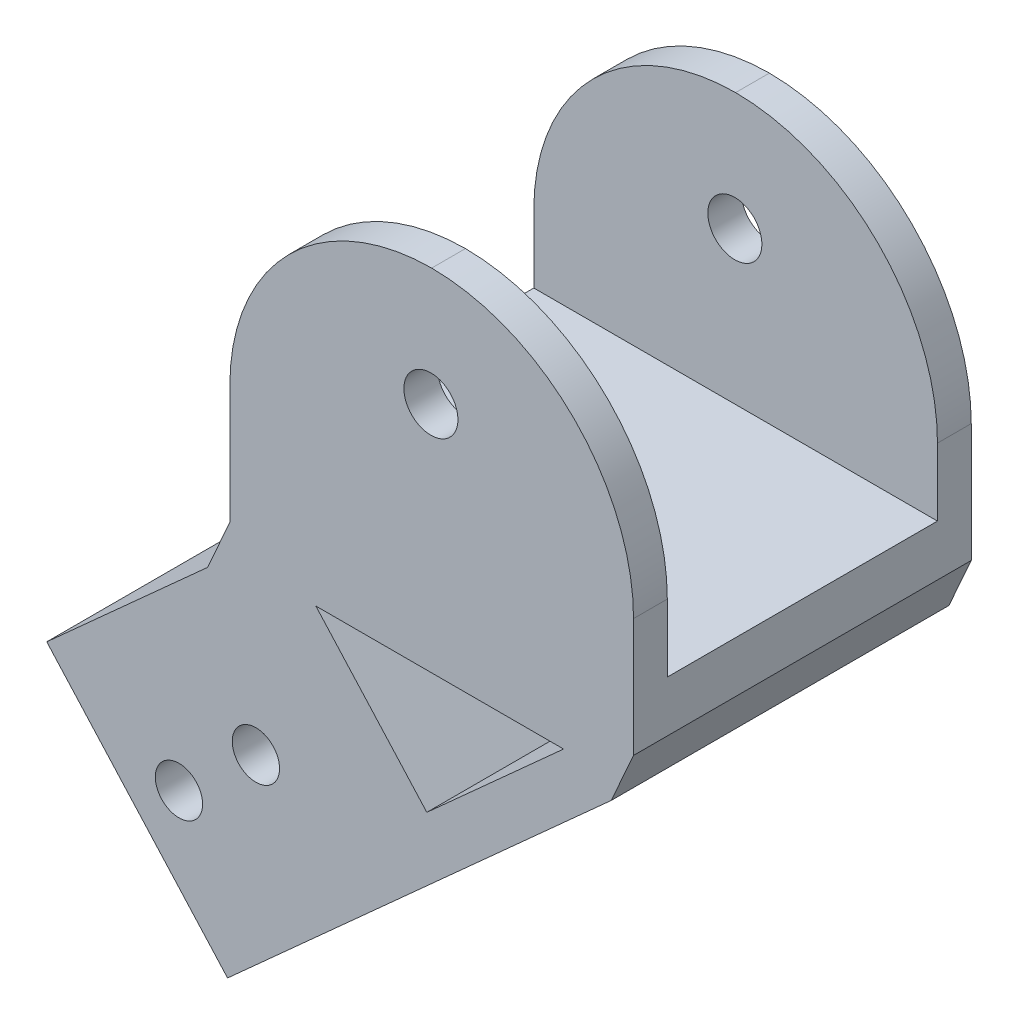
SolidWorks part; units mm, degrees
ref_plane "Front Plane" through (0, 0, 0) normal (0, 0, 1) x (1, 0, 0)
ref_plane "Top Plane" through (0, 0, 0) normal (0, 1, 0) x (1, 0, 0)
ref_plane "Right Plane" through (0, 0, 0) normal (1, 0, 0) x (0, 0, -1)
sketch "Sketch5" plane through (0, 0, 0) normal (0, 0, 1) x (1, 0, 0)
  line L0 (0, 0) -> (0, 50000) construction
  line L1 (0, 0) -> (-37151.4014, -33463.015) construction
  line L2 (0, 53.8338) -> (59.7675, 53.8338)
  line L3 (59.7675, 53.8338) -> (-37.4905, -33.7685)
  line L4 (-37.4905, -33.7685) -> (-64.2609, -4.0473)
  line L5 (0, 53.8338) -> (-64.2609, -4.0473)
  dimension "D1" = 132.01
  dimension "D2" = 40
extrude "Boss-Extrude4" add sketch "Sketch5" along normal blind 50
sketch "Sketch6" plane through (0, 53.8338, 0) normal (0, 1, 0) x (1, 0, 0)
  line L1 (59.7675, 0) -> (0, 0)
  line L2 (59.7675, 0) -> (59.7675, -50)
  line L3 (59.7675, -50) -> (0, -50)
  line L4 (0, 0) -> (0, -50)
  line L5 (29.8837, -50) -> (29.8837, 0) construction
  line L6 (59.7675, -25) -> (0, -25) construction
  point P172 (29.8837, -25)
extrude "Boss-Extrude5" add sketch "Sketch6" along normal blind 52
sketch "Sketch7" plane through (-37.4905, -33.7685, 0) normal (-0.743, -0.6693, 0) x (0, 0, 1)
  line L1 (50, 0) -> (0, 0)
  line L2 (50, 0) -> (50, 40)
  line L3 (50, 40) -> (0, 40)
  line L4 (0, 0) -> (0, 40)
  line L5 (25, 40) -> (25, 0) construction
  line L6 (50, 20) -> (0, 20) construction
  point P132 (25, 20)
extrude "Cut-Extrude2" cut sketch "Sketch7" against normal blind 50
sketch "Sketch9" plane through (-0.3391, -0.3054, 0) normal (-0.743, -0.6693, 0) x (0, 0, 1)
  line L0 (0, 0) -> (50, 0) construction
  line L1 (50, 0) -> (50, 40) construction
  circle A0 centre (25, 20) radius 16
  dimension "D1" = 32
  dimension "D2" = 20
  dimension "D3" = 25
extrude "Cut-Extrude3" cut sketch "Sketch9" against normal blind 39
sketch "Sketch10" plane through (0, 105.8338, 0) normal (0, 1, 0) x (1, 0, 0)
  line L0 (59.7675, -45) -> (0, -45)
  line L1 (59.7675, -50) -> (59.7675, 0) construction
  line L2 (0, 0) -> (0, -50) construction
  line L3 (0, -5) -> (59.7675, -5)
  line L4 (59.7675, 0) -> (0, 0) construction
  line L5 (0, -50) -> (59.7675, -50) construction
  line L6 (59.7675, -5) -> (59.7675, -45)
  line L7 (0, -5) -> (0, -45)
  dimension "D1" = 5
  dimension "D2" = 5
extrude "Cut-Extrude4" cut sketch "Sketch10" against normal blind 50
sketch "Sketch11" plane through (0, 0, 50) normal (0, 0, 1) x (1, 0, 0)
  line L0 (0, 105.8338) -> (59.7675, 105.8338) construction
  line L1 (59.7675, 105.8338) -> (59.7675, 53.8338) construction
  circle A0 centre (29.7675, 88.3338) radius 4
  dimension "D1" = 8
  dimension "D2" = 17.5
  dimension "D3" = 30
extrude "Cut-Extrude5" cut sketch "Sketch11" against normal up to surface (50 mm away) up to face at (15.3477, 58.0742, 0)
sketch "Sketch12" plane through (0, 0, 50) normal (0, 0, 1) x (1, 0, 0)
  line L0 (-0.3391, -0.3054) -> (-27.1095, 29.4157) construction
  line L1 (0, 53.8338) -> (-27.1095, 29.4157) construction
  line L2 (-0.3391, -0.3054) -> (59.7675, 53.8338) construction
  circle A0 centre (3.8557, 30.3898) radius 3.5
  circle A1 centre (-7.5349, 20.1301) radius 3.5
  dimension "D1" = 7
  dimension "D2" = 7
  dimension "D3" = 8.33
  dimension "D4" = 15.33
  dimension "D5" = 20
  dimension "D6" = 20
extrude "Cut-Extrude6" cut sketch "Sketch12" against normal up to surface (50 mm away) up to face at (25.7675, 88.3338, 0)
fillet "Fillet2" radius 30 4 edges at (59.7675, 105.8338, 47.5) (0, 105.8338, 47.5) (0, 105.8338, 2.5) (59.7675, 105.8338, 2.5)
sketch "Sketch17" plane through (0, 55.8338, 0) normal (0, 1, 0) x (1, 0, 0)
  line L1 (0, -45) -> (59.7675, -45)
  line L2 (0, -45) -> (0, -5)
  line L3 (0, -5) -> (59.7675, -5)
  line L4 (59.7675, -45) -> (59.7675, -5)
  line L5 (29.8837, -5) -> (29.8837, -45) construction
  line L6 (0, -25) -> (59.7675, -25) construction
  point P92 (29.8837, -25)
extrude "Boss-Extrude8" add sketch "Sketch17" along normal blind 10
fillet "Chamfer5" radius 10 1 edges at (0, 53.8338, 25) profile chamfer
fillet "Chamfer6" radius 10 1 edges at (59.7675, 53.8338, 25) profile chamfer
sketch "Sketch18" plane through (0, 0, 0) normal (0, 0, -1) x (-1, 0, 0)
  line L0 (-28.644, 25.8002) -> (2.9958, 60.9275)
  line L1 (0.3391, -0.3054) -> (-56.4601, 50.8547) construction
  line L2 (-28.644, 25.8002) -> (-56.4601, 50.8547)
  line L3 (-56.4601, 50.8547) -> (-67.643, 60.9275)
  line L4 (-67.643, 60.9275) -> (2.9958, 60.9275)
  line L5 (-29.1603, 35.6862) -> (-49.4122, 53.9275)
  line L6 (-49.4122, 53.9275) -> (-49.4122, 53.9275)
  line L7 (-49.4122, 53.9275) -> (-12.7301, 53.9275)
  line L8 (-29.1603, 35.6862) -> (-12.7301, 53.9275)
  point P3 (-12.8241, 43.3638)
  dimension "D1" = 7
extrude "Cut-Extrude8" cut sketch "Sketch18" against normal up to surface (50 mm away) contours L5 L8 L7 region at (30.4342, 47.847, 0) up to face at (7.3557, 30.3898, 50)
